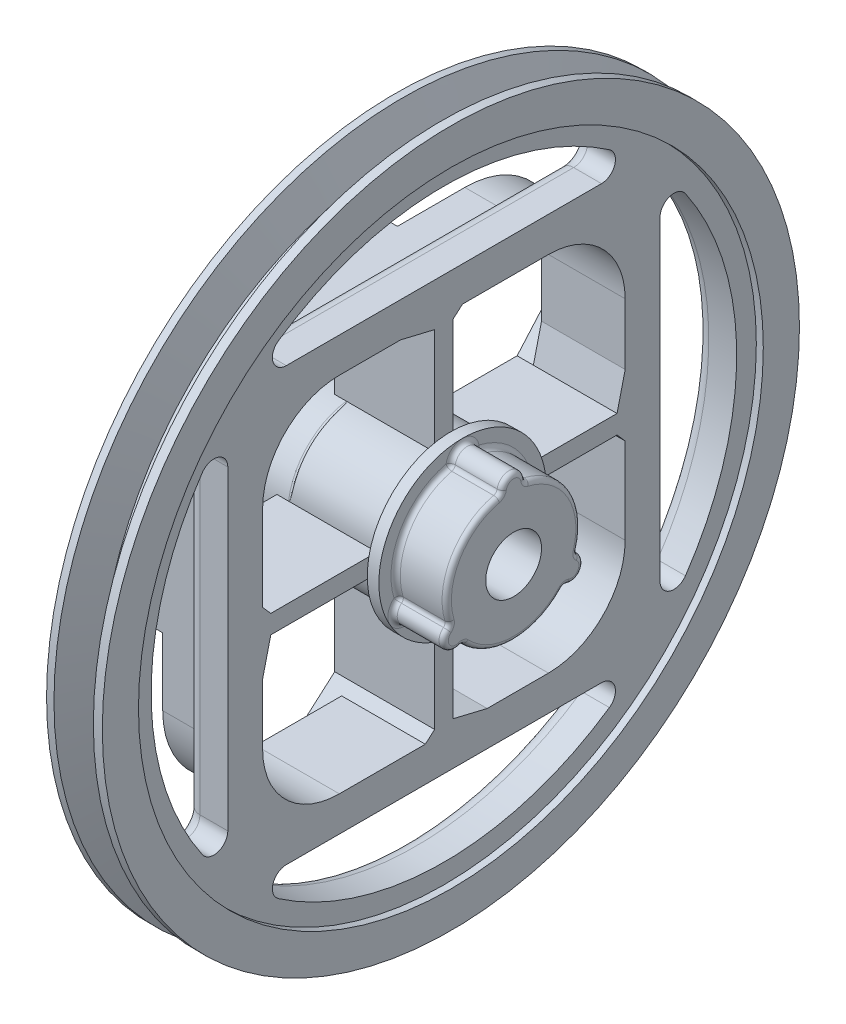
SolidWorks part; units mm, degrees
ref_plane "Ön Düzlem" through (0, 0, 0) normal (0, 0, 1) x (1, 0, 0)
ref_plane "Üst Düzlem" through (0, 0, 0) normal (0, 1, 0) x (1, 0, 0)
ref_plane "Sağ Düzlem" through (0, 0, 0) normal (1, 0, 0) x (0, 0, -1)
sketch "Çizim1" plane through (0, 0, 0) normal (1, 0, 0) x (0, 0, -1)
  circle A0 centre (0, 0) radius 150
  dimension "D1" = 300
extrude "Yükseklik-Ekstrüzyon1" add sketch "Çizim1" along normal blind 88
sketch "Çizim2" plane through (88, 0, 0) normal (1, 0, 0) x (0, 0, -1)
  circle A0 centre (0, 0) radius 13.0153 construction
  circle A1 centre (0, 0) radius 32.5
  circle A2 centre (0, 0) radius 150
  dimension "D1" = 65
extrude "Kes-Ekstrüzyon1" cut sketch "Çizim2" against normal blind 27
sketch "Çizim3" plane through (0, 0, 0) normal (-1, 0, 0) x (0, 0, 1)
  line L1 (-85, 85) -> (85, 85)
  line L2 (-85, 85) -> (-85, -85)
  line L3 (-85, -85) -> (85, -85)
  line L4 (85, 85) -> (85, -85)
  line L5 (-85, 85) -> (85, -85) construction
  line L6 (-85, -85) -> (85, 85) construction
  circle A0 centre (0, 0) radius 157.6315
  point P0 (0, 0)
  dimension "D1" = 170
extrude "Kes-Ekstrüzyon2" cut sketch "Çizim3" against normal blind 37
fillet "Radyus1" radius 40 4 edges at (18.5, -85, 85) (18.5, 85, 85) (18.5, -85, -85) (18.5, 85, -85)
sketch "Çizim4" plane through (0, 0, 0) normal (-1, 0, 0) x (0, 0, 1)
  circle A0 centre (0, 0) radius 12
extrude "Kes-Ekstrüzyon3" cut sketch "Çizim4" against normal blind 276
sketch "Çizim5" plane through (0, 0, 0) normal (-1, 0, 0) x (0, 0, 1)
  line L0 (0, 12) -> (0, 85) construction
  line L1 (45, 85) -> (-45, 85) construction
  line L2 (-16, 85) -> (16, 85)
  line L3 (16, 85) -> (4, 74.5)
  line L4 (-4, 74.5) -> (-16, 85)
  line L5 (4, 11.3137) -> (4, 74.5)
  line L6 (-4, 11.3137) -> (-4, 74.5)
  line L7 (4, 0) -> (4, 85) construction
  line L8 (-4, 0) -> (-4, 85) construction
  line L9 (0, 0) -> (0, 85) construction
  line L10 (11.3137, 4) -> (74.5, 4)
  line L11 (11.3137, -4) -> (74.5, -4)
  line L12 (85, -16) -> (74.5, -4)
  line L13 (74.5, 4) -> (85, 16)
  line L14 (85, 16) -> (85, -16)
  line L15 (4, -11.3137) -> (4, -74.5)
  line L16 (-4, -11.3137) -> (-4, -74.5)
  line L17 (-16, -85) -> (-4, -74.5)
  line L18 (4, -74.5) -> (16, -85)
  line L19 (16, -85) -> (-16, -85)
  line L20 (-11.3137, -4) -> (-74.5, -4)
  line L21 (-11.3137, 4) -> (-74.5, 4)
  line L22 (-85, 16) -> (-74.5, 4)
  line L23 (-74.5, -4) -> (-85, -16)
  line L24 (-85, -16) -> (-85, 16)
  line L29 (-45, -85) -> (45, -85)
  line L30 (85, -45) -> (85, 45)
  line L31 (45, 85) -> (-45, 85)
  line L32 (-85, 45) -> (-85, -45)
  line L33 (-45, -85) -> (45, -85)
  line L34 (85, -45) -> (85, 45)
  line L35 (45, 85) -> (-45, 85)
  line L36 (-85, 45) -> (-85, -45)
  arc A0 (-11.3137, -4) -> (-4, -11.3137) centre (0, 0) ccw
  arc A1 (4, -11.3137) -> (-11.3137, 4) centre (0, 0) ccw
  arc A6 (45, -85) -> (85, -45) centre (45, -45) ccw
  arc A7 (85, 45) -> (45, 85) centre (45, 45) ccw
  arc A8 (-45, 85) -> (-85, 45) centre (-45, 45) ccw
  arc A9 (-85, -45) -> (-45, -85) centre (-45, -45) ccw
  arc A10 (45, -85) -> (85, -45) centre (45, -45) ccw
  arc A11 (85, 45) -> (45, 85) centre (45, 45) ccw
  arc A12 (-45, 85) -> (-85, 45) centre (-45, 45) ccw
  arc A13 (-85, -45) -> (-45, -85) centre (-45, -45) ccw
  point P38 (0, 0)
  circle M11 centre (0, 0) radius 12
  line M12 (-45, -85) -> (45, -85)
  arc M13 (45, -85) -> (85, -45) centre (45, -45) ccw
  line M14 (85, -45) -> (85, 45)
  arc M15 (85, 45) -> (45, 85) centre (45, 45) ccw
  line M16 (45, 85) -> (-45, 85)
  arc M17 (-45, 85) -> (-85, 45) centre (-45, 45) ccw
  line M18 (-85, 45) -> (-85, -45)
  arc M19 (-85, -45) -> (-45, -85) centre (-45, -45) ccw
  dimension "D1" = 32
  dimension "D4" = 4
  dimension "D2" = 4
  dimension "D3" = 4
  dimension "D5" = 0
extrude "Kes-Ekstrüzyon4" cut sketch "Çizim5" against normal blind 22 contours L22 L21 L6 L4 M18 M11 M16 M17 | L10 L13 L3 L5 M14 M15 M16 M11 | L15 L18 L12 L11 M12 M13 M14 M11 | L20 L23 L17 L16 M18 M19 M12 M11 region at (0, 42.9226, -42.9226) region at (0, 42.9226, 42.9226) region at (0, -42.9226, -42.9226) region at (0, -42.9226, 42.9226)
sketch "Çizim6" plane through (0, 0, 0) normal (-1, 0, 0) x (0, 0, 1)
  circle A0 centre (0, 0) radius 29.1305
  circle A1 centre (0, 0) radius 12
extrude "Yükseklik-Ekstrüzyon2" add sketch "Çizim6" against normal blind 33
sketch "Çizim7" plane through (0, 0, 0) normal (0, 0, 1) x (1, 0, 0)
  line L0 (57.1353, 150) -> (51.5809, 135.6862)
  line L1 (61, 150) -> (37, 150) construction
  line L2 (51.5809, 135.6862) -> (45.7417, 135.6862)
  line L3 (45.7417, 135.6862) -> (40.1873, 150)
  line L4 (40.1873, 150) -> (57.1353, 150)
  line L5 (0, 0) -> (154.4931, 0) construction
revolve "Kes-Döndür1" cut sketch "Çizim7" angle 360 about L5
sketch "Çizim8" plane through (37, 0, 0) normal (-1, 0, 0) x (0, 0, 1)
  line L0 (-85.0118, 93) -> (85.0118, 93)
  circle A0 centre (0, 0) radius 126 construction
  arc A1 (85.0118, 93) -> (-85.0118, 93) centre (0, 0) ccw
  circle A2 centre (0, 0) radius 150
  circle A3 centre (0, 0) radius 150 construction
  point P7 (0, 126)
  dimension "D3" = 33
  dimension "D1" = 0
  dimension "D2" = 24
extrude "Kes-Ekstrüzyon5" cut sketch "Çizim8" against normal blind 52
fillet "Radyus2" radius 6 2 edges at (49, 93, 85.0118) (49, 93, -85.0118)
pattern_circular "Dairesel Kaplama1" count 4 over 360 about axis through (37, 0, 0) along (-1, 0, 0) of "Radyus2", "Kes-Ekstrüzyon5"
sketch "Çizim9" plane through (37, 0, 0) normal (-1, 0, 0) x (0, 0, 1)
  line L0 (45, 85) -> (-45, 85) construction
  line L1 (85, -45) -> (85, 45) construction
  line L2 (-45, -85) -> (45, -85) construction
  line L3 (-85, 45) -> (-85, -45) construction
  line L6 (45, 85) -> (-45, 85)
  line L7 (85, -45) -> (85, 45)
  line L8 (-45, -85) -> (45, -85)
  line L9 (-85, 45) -> (-85, -45)
  circle A0 centre (0, 0) radius 135
  arc A1 (85, 45) -> (45, 85) centre (45, 45) ccw construction
  arc A2 (45, -85) -> (85, -45) centre (45, -45) ccw construction
  arc A3 (-85, -45) -> (-45, -85) centre (-45, -45) ccw construction
  arc A4 (-45, 85) -> (-85, 45) centre (-45, 45) ccw construction
  arc A5 (85, 45) -> (45, 85) centre (45, 45) ccw
  arc A6 (45, -85) -> (85, -45) centre (45, -45) ccw
  arc A7 (-85, -45) -> (-45, -85) centre (-45, -45) ccw
  arc A8 (-45, 85) -> (-85, 45) centre (-45, 45) ccw
  dimension "D1" = 270
extrude "Kes-Ekstrüzyon7" cut sketch "Çizim9" against normal blind 3
fillet "Radyus3" radius 6 16 edges at (40, -97.2252, 73.5474) (40, -93, 0) (40, -97.2252, -73.5474) (40, -73.5474, 97.2252) (40, 0, 126) (40, 73.5474, 97.2252) (40, 73.5474, -97.2252) (40, 0, -126) (40, -73.5474, -97.2252) (40, 97.2252, 73.5474) (40, 126, 0) (40, 97.2252, -73.5474) (40, -126, 0) (40, 0, 93) (40, 0, -93) (40, 93, 0)
sketch "Çizim11" plane through (22, 0, 0) normal (-1, 0, 0) x (0, 0, 1)
  line L0 (-78, 45) -> (-78, 18.6301)
  line L5 (-18.6301, 78) -> (-45, 78)
  line L6 (-4, 28.8545) -> (-4, 74.5)
  line L7 (-4, 74.5) -> (-16, 85)
  line L8 (-16, 85) -> (-45, 85)
  line L9 (-85, 45) -> (-85, 16)
  line L10 (-85, 16) -> (-74.5, 4)
  line L11 (-74.5, 4) -> (-28.8545, 4)
  line L12 (-4, 28.8545) -> (-4, 74.5) construction
  line L13 (-4, 74.5) -> (-16, 85) construction
  line L14 (-16, 85) -> (-45, 85) construction
  line L15 (-85, 45) -> (-85, 16) construction
  line L16 (-85, 16) -> (-74.5, 4) construction
  line L17 (-74.5, 4) -> (-28.8545, 4) construction
  line L19 (-74.5, 4) -> (-28.8545, 4)
  line L20 (-4, 28.8545) -> (-4, 74.5)
  line L21 (-4, 74.5) -> (-8, 78)
  line L22 (-8, 78) -> (-18.6301, 78)
  line L23 (-78, 18.6301) -> (-74.5, 4)
  line L24 (-11, 71.3236) -> (-18.6301, 78) construction
  line L25 (-11, 34.4153) -> (-11, 71.3236) construction
  line L26 (-71.3236, 11) -> (-34.4153, 11) construction
  line L32 (-78, 18.6301) -> (-71.3236, 11) construction
  arc A0 (-45, 78) -> (-78, 45) centre (-45, 45) ccw
  arc A2 (-4, 28.8545) -> (-28.8545, 4) centre (0, 0) ccw
  arc A3 (-45, 85) -> (-85, 45) centre (-45, 45) ccw
  arc A4 (-4, 28.8545) -> (-28.8545, 4) centre (0, 0) ccw construction
  arc A5 (-45, 85) -> (-85, 45) centre (-45, 45) ccw construction
  arc A6 (-28.8545, 4) -> (-4, 28.8545) centre (-4, 4) cw
  arc A8 (-11, 34.4153) -> (-34.4153, 11) centre (0, 0) ccw construction
  dimension "D1" = 0
  dimension "D2" = 7
extrude "Kes-Ekstrüzyon8" cut sketch "Çizim11" against normal blind 159
pattern_circular "Dairesel Kaplama2" count 4 over 360 about axis through (37, 0, 0) along (-1, 0, 0) of "Kes-Ekstrüzyon8"
sketch "Çizim12" plane through (0, 0, 0) normal (-1, 0, 0) x (0, 0, 1)
  circle A0 centre (0, 0) radius 29.1305
  circle A1 centre (0, 0) radius 110.2804
extrude "Kes-Ekstrüzyon9" cut sketch "Çizim12" against normal blind 15
sketch "Çizim13" plane through (61, 0, 0) normal (1, 0, 0) x (0, 0, -1)
  circle A0 centre (0, 0) radius 36
  dimension "D1" = 72
extrude "Yükseklik-Ekstrüzyon3" add sketch "Çizim13" along normal blind 5
sketch "Çizim14" plane through (88, 0, 0) normal (1, 0, 0) x (0, 0, -1)
  circle A0 centre (0, 0) radius 28.7847
  circle A1 centre (0, 0) radius 39.2273
extrude "Kes-Ekstrüzyon10" cut sketch "Çizim14" against normal up to surface (22 mm away) up to face at (66, 0, 0)
sketch "Çizim15" plane through (88, 0, 0) normal (1, 0, 0) x (0, 0, -1)
  circle A0 centre (0, 28.7847) radius 5.1646
  circle A1 centre (0, 0) radius 28.7847 construction
extrude "Yükseklik-Ekstrüzyon4" add sketch "Çizim15" against normal up to surface (22 mm away) up to face at (66, 0, -36)
pattern_circular "Dairesel Kaplama3" count 3 over 360 about axis through (88, 0, 0) along (1, 0, 0) of "Yükseklik-Ekstrüzyon4"
fillet "Radyus4" radius 2 20 edges at (88, -16.9747, 29.401) (88, 33.9493, 0) (66, 33.9493, 0) (66, 14.3923, 24.9283) (77, 28.3214, 5.1438) (88, 14.3923, 24.9283) (77, -18.6153, 21.9551) (77, -9.706, 27.0989) (88, -16.9747, -29.401) (66, -16.9747, -29.401) (66, -28.7847, 0) (88, -28.7847, 0) (77, -9.706, -27.0989) (77, -18.6153, -21.9551) (88, 14.3923, -24.9283) (77, 28.3214, -5.1438) (66, 14.3923, -24.9283) (66, -16.9747, 29.401) (22, 20.5984, 20.5984) (0, 0, 29.1305)
sketch "Çizim16" plane through (61, 0, 0) normal (1, 0, 0) x (0, 0, -1)
  circle A0 centre (0, 0) radius 134.4443
extrude "Kes-Ekstrüzyon11" cut sketch "Çizim16" against normal blind 3
